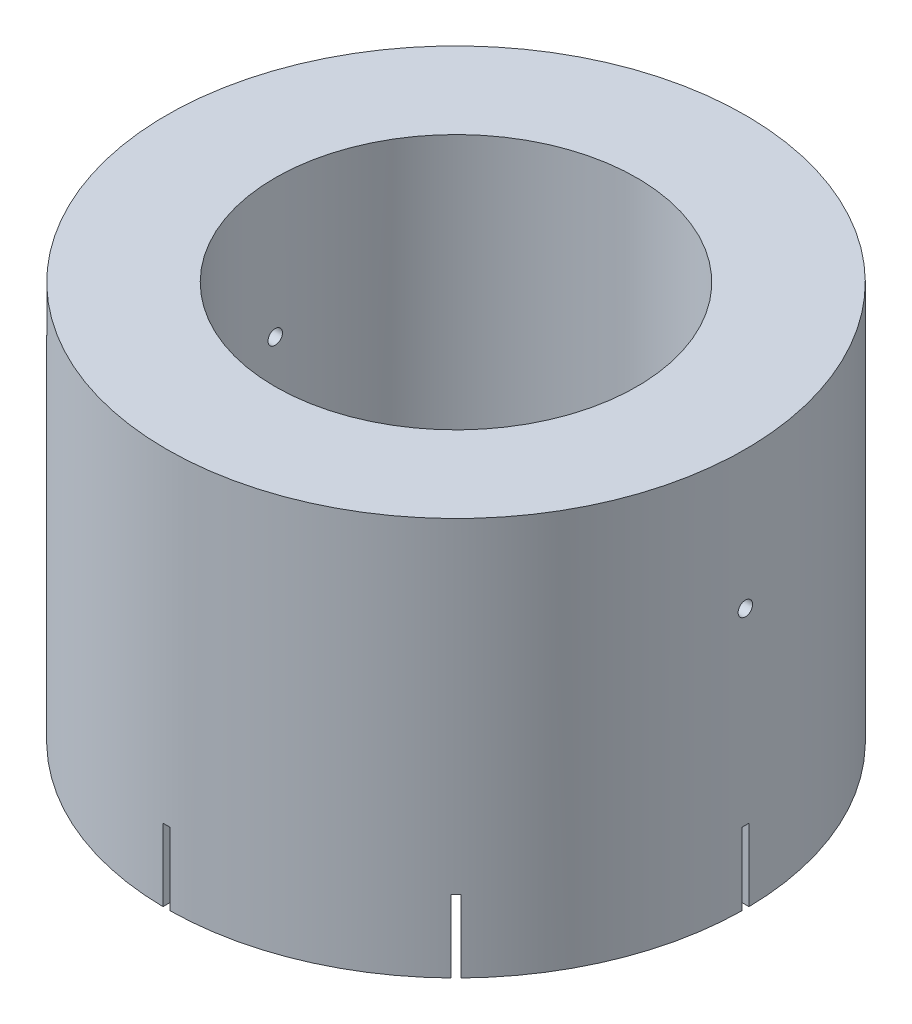
SolidWorks part; units mm, degrees
material "C (Graphite)"
ref_plane "Front Plane" through (0, 0, 0) normal (0, 0, 1) x (1, 0, 0)
ref_plane "Top Plane" through (0, 0, 0) normal (0, 1, 0) x (1, 0, 0)
ref_plane "Right Plane" through (0, 0, 0) normal (1, 0, 0) x (0, 0, -1)
sketch "Sketch1" plane through (0, 0, 0) normal (0, 1, 0) x (1, 0, 0)
  circle A0 centre (0, 0) radius 40
  circle A1 centre (0, 0) radius 25
  dimension "D1" = 80
  dimension "D2" = 50
extrude "Boss-Extrude1" add sketch "Sketch1" along normal blind 50
sketch "Sketch2" plane through (0, 0, 0) normal (0, -1, 0) x (1, 0, 0)
  circle A0 centre (0, 0) radius 37.5
  circle A1 centre (0, 0) radius 40
  dimension "D1" = 75
  dimension "D2" = 80
extrude "Boss-Extrude2" add sketch "Sketch2" along normal blind 5
sketch "Sketch3" plane through (0, 0, 0) normal (1, 0, 0) x (0, 0, -1)
  line L0 (40, 50) -> (-40, 50) construction
  circle A0 centre (0, 30.95) radius 1
  dimension "D1" = 2
  dimension "D2" = 19.05
extrude "Cut-Extrude2" cut sketch "Sketch3" against normal through all both and the other way through all
sketch "Sketch4" plane through (0, 0, 0) normal (0, 0, 1) x (1, 0, 0)
  line L0 (-40, -5) -> (40, -5) construction
  line L1 (-0.5, -5) -> (0.5, -5)
  line L2 (-0.5, -5) -> (-0.5, 5)
  line L3 (-0.5, 5) -> (0.5, 5)
  line L4 (0.5, -5) -> (0.5, 5)
  line L5 (0, -30.25) -> (0, 30.25) construction
  point P6 (0, 5)
  dimension "D1" = 0
  dimension "D2" = 1
  dimension "D3" = 10
extrude "Cut-Extrude3" cut sketch "Sketch4" against normal through all both and the other way through all
pattern_circular "CirPattern1" count 4 every 45 about axis through (0, 50, 0) along (0, -1, 0) of "Cut-Extrude3"
